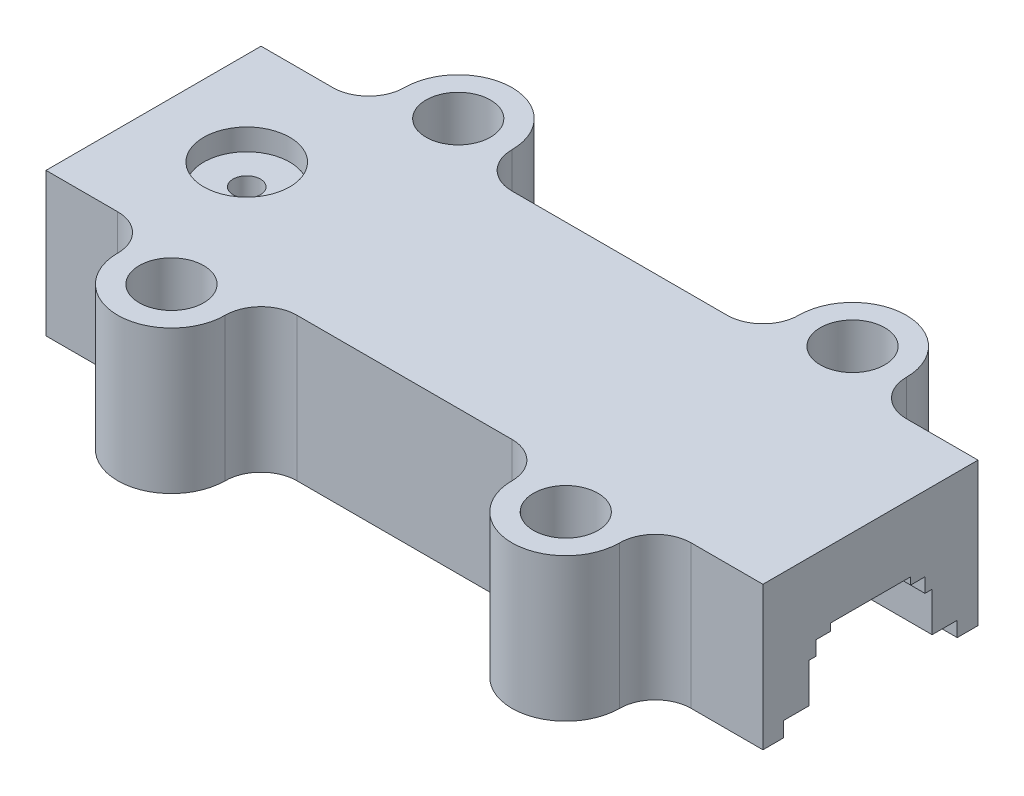
SolidWorks part; units mm, degrees
ref_plane "Front Plane" through (0, 0, 0) normal (0, 0, 1) x (1, 0, 0)
ref_plane "Top Plane" through (0, 0, 0) normal (0, 1, 0) x (1, 0, 0)
ref_plane "Right Plane" through (0, 0, 0) normal (1, 0, 0) x (0, 0, -1)
sketch "Sketch1" plane through (0, 0, 0) normal (0, 1, 0) x (1, 0, 0)
  line L1 (0, 15) -> (100, 15)
  line L2 (0, 15) -> (0, -15)
  line L3 (0, -15) -> (100, -15)
  line L4 (100, 15) -> (100, -15)
  point P4 (0, 0)
  dimension "D1" = 30
  dimension "D2" = 100
extrude "Boss-Extrude1" add sketch "Sketch1" along normal blind 20
sketch "Sketch2" plane through (100, 0, 0) normal (1, 0, 0) x (0, 0, -1)
  line L1 (-7.6, 0) -> (7.6, 0)
  line L2 (-7.6, 0) -> (-7.6, 9.6)
  line L3 (-7.6, 9.6) -> (7.6, 9.6)
  line L4 (7.6, 0) -> (7.6, 9.6)
  point P4 (0, 0)
  dimension "D1" = 15.2
  dimension "D2" = 9.6
extrude "Cut-Extrude1" cut sketch "Sketch2" against normal through all
sketch "Sketch3" plane through (100, 0, 0) normal (1, 0, 0) x (0, 0, -1)
  line L0 (-15, 20) -> (-15, 0) construction
  line L1 (-7.6, 0) -> (-12.1, 0)
  line L2 (-7.6, 0) -> (-7.6, 2.1)
  line L3 (-7.6, 2.1) -> (-12.1, 2.1)
  line L4 (-12.1, 0) -> (-12.1, 2.1)
  line L5 (7.6, 0) -> (15, 0) construction
  line L6 (12.1, 0) -> (7.6, 0)
  line L7 (12.1, 0) -> (12.1, 2.1)
  line L8 (12.1, 2.1) -> (7.6, 2.1)
  line L9 (7.6, 0) -> (7.6, 2.1)
  line L10 (7.6, 0) -> (7.6, 9.6) construction
  line L11 (15, 20) -> (15, 0) construction
  line L12 (7.6, 9.6) -> (-7.6, 9.6) construction
  line L13 (-7.6, 2.1) -> (-8.6, 2.1)
  line L14 (-7.6, 2.1) -> (-7.6, 7.6)
  line L15 (-7.6, 7.6) -> (-8.6, 7.6)
  line L16 (-8.6, 2.1) -> (-8.6, 7.6)
  line L17 (-7.6, 9.6) -> (-7.6, 0) construction
  line L18 (7.6, 2.1) -> (8.6, 2.1)
  line L19 (7.6, 2.1) -> (7.6, 7.6)
  line L20 (7.6, 7.6) -> (8.6, 7.6)
  line L21 (8.6, 2.1) -> (8.6, 7.6)
  line L22 (-5.6, 9.6) -> (5.6, 9.6)
  line L23 (-5.6, 9.6) -> (-5.6, 10.6)
  line L24 (-5.6, 10.6) -> (5.6, 10.6)
  line L25 (5.6, 9.6) -> (5.6, 10.6)
  line M1 (-15, 0) -> (-7.6, 0)
  line M2 (-7.6, 0) -> (-7.6, 9.6)
  line M3 (-7.6, 9.6) -> (7.6, 9.6)
  line M4 (7.6, 9.6) -> (7.6, 0)
  line M5 (7.6, 0) -> (15, 0)
  dimension "D1" = 2.1
  dimension "D2" = 2.9
  dimension "D3" = 2.9
  dimension "D4" = 2.1
  dimension "D5" = 1
  dimension "D6" = 2
  dimension "D7" = 1
  dimension "D8" = 2
  dimension "D9" = 1
  dimension "D10" = 2
  dimension "D11" = 2
extrude "Cut-Extrude2" cut sketch "Sketch3" against normal through all contours L16 L3 L15 M2 | L8 L21 L20 M4 | L7 L8 M4 M5 | L4 L3 M1 M2 | L25 L24 L23 M3 region at (100, 4.85, -8.1) region at (100, 10.1, 0) region at (100, 1.05, 9.85) region at (100, 4.85, 8.1) region at (100, 1.05, -9.85)
sketch "Sketch4" plane through (0, 0, 0) normal (0, -1, 0) x (1, 0, 0)
  line L0 (0, 12.1) -> (100, 12.1) construction
  line L1 (0, -12.1) -> (5, -12.1)
  line L2 (0, -12.1) -> (0, 12.1)
  line L3 (0, 12.1) -> (5, 12.1)
  line L4 (5, -12.1) -> (5, 12.1)
  dimension "D1" = 5
extrude "Boss-Extrude2" add sketch "Sketch4" against normal up to next
sketch "Sketch6" plane through (0, 0, 0) normal (0, -1, 0) x (1, 0, 0)
  line L0 (5, -12.1) -> (100, -12.1) construction
  line L1 (5, 12.1) -> (2.9, 12.1)
  line L2 (5, 12.1) -> (5, -12.1)
  line L3 (5, -12.1) -> (2.9, -12.1)
  line L4 (2.9, 12.1) -> (2.9, -12.1)
  line L5 (0, -15) -> (0, 15) construction
  dimension "D1" = 2.9
extrude "Cut-Extrude3" cut sketch "Sketch6" against normal up to surface (2.1 mm away) up to face at (52.5, 2.1, 10.35)
sketch "Sketch9" plane through (0, 9.6, 0) normal (0, -1, 0) x (1, 0, 0)
  line L0 (5, -5.6) -> (100, -5.6) construction
  line L1 (5, 5.6) -> (24.05, 5.6)
  line L2 (5, 5.6) -> (5, -5.6)
  line L3 (5, -5.6) -> (24.05, -5.6)
  line L4 (24.05, 5.6) -> (24.05, -5.6)
  dimension "D1" = 19.05
extrude "Boss-Extrude3" add sketch "Sketch9" against normal up to next
fillet "Fillet1" radius 1.5875 4 edges at (5, 4.85, -8.6) (5, 4.85, 8.6) (2.9, 1.05, -12.1) (2.9, 1.05, 12.1)
fillet "Fillet2" radius 1.5875 2 edges at (5.1127, 8.6, -7.6) (5.1127, 8.6, 7.6)
sketch "Sketch7" plane through (0, 9.6, 0) normal (0, -1, 0) x (1, 0, 0)
  line L1 (5, -6.0125) -> (5, 6.0125) construction
  circle A0 centre (13, 0) radius 1.905
  dimension "D1" = 3.81
  dimension "D2" = 8
extrude "Cut-Extrude4" cut sketch "Sketch7" against normal through all
sketch "Sketch10" plane through (0, 9.6, 0) normal (0, -1, 0) x (1, 0, 0)
  circle A0 centre (13, 0) radius 3.25
  circle A3 centre (13, 0) radius 1.905 construction
  dimension "D1" = 6.5
extrude "Cut-Extrude6" cut sketch "Sketch10" against normal blind 4
sketch "Sketch8" plane through (0, 20, 0) normal (0, 1, 0) x (1, 0, 0)
  circle A0 centre (13, 0) radius 6
  dimension "D1" = 12
extrude "Cut-Extrude5" cut sketch "Sketch8" against normal blind 3
fillet "Fillet5" radius 1.5875 2 edges at (24.05, 10.1, -5.6) (24.05, 10.1, 5.6)
sketch "Sketch11" plane through (0, 20, 0) normal (0, 1, 0) x (1, 0, 0)
  line L4 (30, -20) -> (30, -15)
  line L5 (15, -15) -> (15, -20)
  line L6 (70, -15) -> (70, -20)
  line L7 (85, -20) -> (85, -15)
  line L8 (15, -15) -> (30, -15)
  line L9 (70, -15) -> (85, -15)
  line L11 (0, 15) -> (0, -15) construction
  line L12 (100, -15) -> (100, 15) construction
  line L13 (0, -15) -> (100, -15) construction
  arc A2 (15, -20) -> (30, -20) centre (22.5, -20) ccw
  arc A3 (70, -20) -> (85, -20) centre (77.5, -20) ccw
  dimension "D1" = 15
  dimension "D2" = 15
  dimension "D3" = 15
  dimension "D4" = 15
  dimension "D5" = 5
extrude "Boss-Extrude4" add sketch "Sketch11" against normal up to surface (20 mm away) up to face at (41.4117, 0, 0)
sketch "Sketch12" plane through (0, 20, 0) normal (0, 1, 0) x (1, 0, 0)
  circle A0 centre (22.5, -20) radius 4.5
  circle A1 centre (77.5, -20) radius 4.5
  dimension "D1" = 9
extrude "Cut-Extrude7" cut sketch "Sketch12" against normal blind 8
sketch "Sketch13" plane through (0, 12, 0) normal (0, 1, 0) x (1, 0, 0)
  circle A0 centre (22.5, -20) radius 2.75
  circle A1 centre (77.5, -20) radius 2.75
  dimension "D1" = 5.5
extrude "Cut-Extrude8" cut sketch "Sketch13" against normal through all
mirror "Mirror1" about plane through (0, 0, 0) normal (0, 0, 1) of "Boss-Extrude4", "Cut-Extrude7", "Cut-Extrude8"
fillet "Fillet6" radius 5 8 edges at (70, 10, 15) (85, 10, 15) (85, 10, -15) (70, 10, -15)
